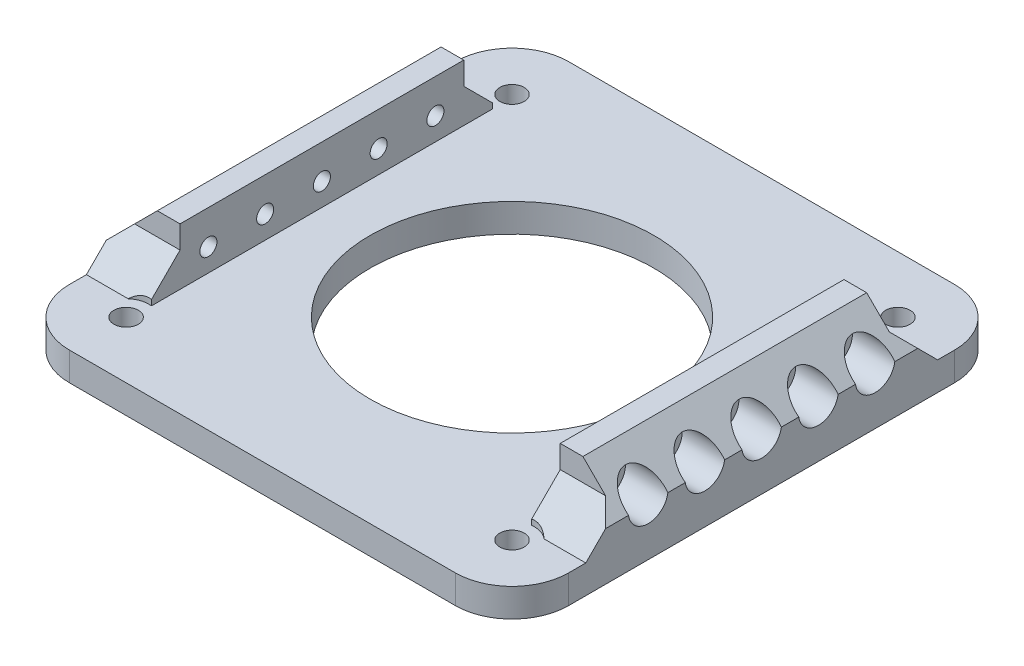
SolidWorks part; units mm, degrees
ref_plane "Front Plane" through (0, 0, 0) normal (0, 0, 1) x (1, 0, 0)
ref_plane "Top Plane" through (0, 0, 0) normal (0, 1, 0) x (1, 0, 0)
ref_plane "Right Plane" through (0, 0, 0) normal (1, 0, 0) x (0, 0, -1)
sketch "Sketch1" plane through (0, 0, 0) normal (0, 1, 0) x (1, 0, 0)
  line L1 (44, -44) -> (-44, -44)
  line L2 (44, -44) -> (44, 44)
  line L3 (44, 44) -> (-44, 44)
  line L4 (-44, -44) -> (-44, 44)
  line L5 (44, -44) -> (-44, 44) construction
  line L6 (44, 44) -> (-44, -44) construction
  point P0 (0, 0)
  dimension "D1" = 88
extrude "Boss-Extrude1" add sketch "Sketch1" along normal blind 5
fillet "Fillet1" radius 10 4 edges at (-44, 2.5, -44) (44, 2.5, -44) (-44, 2.5, 44) (44, 2.5, 44)
sketch "Sketch2" plane through (0, 5, 0) normal (0, 1, 0) x (1, 0, 0)
  circle A0 centre (34, 34) radius 2.15
  circle A1 centre (34, -34) radius 2.15
  circle A2 centre (-34, -34) radius 2.15
  circle A3 centre (-34, 34) radius 2.15
  dimension "D1" = 4.3
extrude "Cut-Extrude1" cut sketch "Sketch2" against normal through all
sketch "Sketch3" plane through (0, 5, 0) normal (0, 1, 0) x (1, 0, 0)
  line L0 (0, -1000) -> (0, 49000) construction
  line L1 (-37.5, -25) -> (-33.5, -25)
  line L2 (-37.5, -25) -> (-37.5, 25)
  line L3 (-37.5, 25) -> (-33.5, 25)
  line L4 (-33.5, -25) -> (-33.5, 25)
  line L5 (-37.5, -25) -> (-33.5, 25) construction
  line L6 (-37.5, 25) -> (-33.5, -25) construction
  line L7 (33.5, -25) -> (37.5, -25)
  line L8 (33.5, -25) -> (33.5, 25)
  line L9 (33.5, 25) -> (37.5, 25)
  line L10 (37.5, -25) -> (37.5, 25)
  line L11 (33.5, -25) -> (37.5, 25) construction
  line L12 (33.5, 25) -> (37.5, -25) construction
  point P0 (-35.5, 0)
  point P5 (35.5, 0)
  point P23 (0, 0)
  point P24 (-18.6, 19.0576)
  point P25 (0, 0)
  point P26 (22.6, 18.487)
  dimension "D1" = 67
  dimension "D2" = 4
  dimension "D4" = 50
extrude "Boss-Extrude2" add sketch "Sketch3" along normal blind 10
chamfer "Chamfer1" distance 10 angle 45 2 edges at (37.5, 5, 0) (-37.5, 5, 0)
sketch "Sketch4" plane through (0, 0, 0) normal (1, 0, 0) x (0, 0, -1)
  line L0 (-25, 8.5) -> (-25, 15) construction
  line L1 (-34, 5) -> (-25, 5) construction
  circle A0 centre (-20, 9) radius 1.5
  point P2 (-19.0831, 10.7752)
  dimension "D1" = 3
  dimension "D2" = 5
  dimension "D3" = 4
extrude "Cut-Extrude2" cut sketch "Sketch4" against normal through all and the other way through all
sketch "Sketch5" plane through (44, 0, 0) normal (1, 0, 0) x (0, 0, -1)
  circle A0 centre (-20, 9) radius 3.5
  dimension "D1" = 7
extrude "Cut-Extrude3" cut sketch "Sketch5" against normal offset from surface (7.5 mm away) 3 up to face at (33.5, 9, 18.5)
sketch "Sketch6" plane through (-44, 0, 0) normal (-1, 0, 0) x (0, 0, 1)
  circle A0 centre (20, 9) radius 3.5
  dimension "D1" = 7
extrude "Cut-Extrude4" cut sketch "Sketch6" against normal offset from surface (7.5 mm away) 3 up to face at (-33.5, 9, 21.5)
pattern_linear "LPattern2" count 5 spacing 10 along (0, 0, -1) of "Cut-Extrude2", "Cut-Extrude3", "Cut-Extrude4"
chamfer "Chamfer2" distance 6 angle 45 4 edges at (-38.75, 5, 25) (-38.75, 5, -25) (38.75, 5, -25) (38.75, 5, 25)
sketch "Sketch7" plane through (0, 5, 0) normal (0, 1, 0) x (1, 0, 0)
  circle A0 centre (0, 0) radius 25
  dimension "D1" = 50
extrude "Cut-Extrude5" cut sketch "Sketch7" against normal through all
sketch "Sketch8" plane through (0, 5, 0) normal (0, 1, 0) x (1, 0, 0)
  circle A0 centre (-34, -34) radius 4
  circle A1 centre (34, -34) radius 4
  circle A2 centre (34, 34) radius 4
  circle A3 centre (-34, 34) radius 4
  dimension "D1" = 8
extrude "Cut-Extrude6" cut sketch "Sketch8" along normal through all
